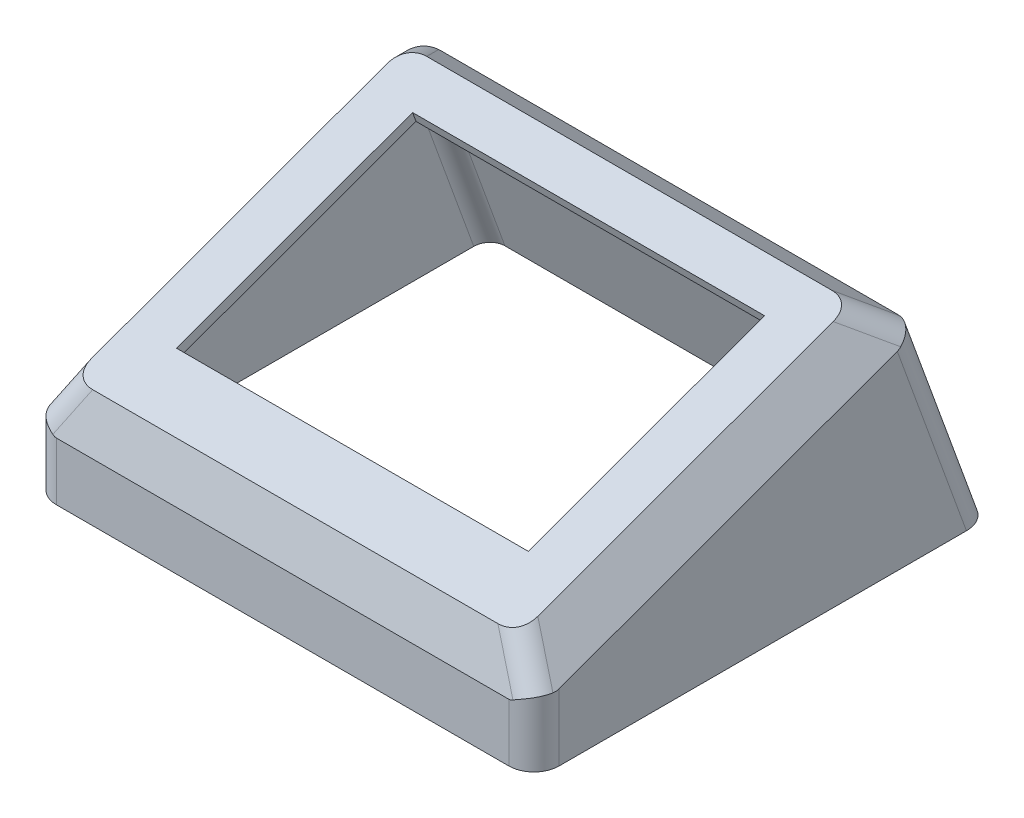
SolidWorks part; units mm, degrees
ref_plane "Front Plane" through (0, 0, 0) normal (0, 0, 1) x (1, 0, 0)
ref_plane "Top Plane" through (0, 0, 0) normal (0, 1, 0) x (1, 0, 0)
ref_plane "Right Plane" through (0, 0, 0) normal (1, 0, 0) x (0, 0, -1)
sketch "Sketch2" plane through (0, 0, 0) normal (1, 0, 0) x (0, 0, -1)
  line L0 (-74.2357, 0) -> (-74.2357, 20)
  line L1 (55, 0) -> (-55, 0) construction
  line L2 (-74.2357, 20) -> (0, 47.0196)
  line L3 (0, 55) -> (0, -55) construction
  line L4 (0, 47.0196) -> (17.1137, 0)
  line L5 (17.1137, 0) -> (-74.2357, 0)
  dimension "D1" = 79
  dimension "D2" = 20
  dimension "D3" = 110
extrude "Boss-Extrude1" add sketch "Sketch2" along normal blind 50 and the other way blind 50
chamfer "Chamfer3" distance 8 angle 35 3 edges at (50, 33.5098, 37.1179) (0, 47.0196, 0) (-50, 33.5098, 37.1179) first distance on face at (50, 16.7549, 32.8394) first distance on face at (0, 23.5098, -8.5569) first distance on face at (-50, 16.7549, 32.8394)
chamfer "Chamfer4" distance 8.5 angle 15 1 edges at (0, 20, 74.2357) first distance on face at (0, 10.4955, 74.2357)
fillet "Fillet7" radius 5 8 edges at (-50, 19.751, -9.9249) (50, 19.751, -9.9249) (-50, 5.7433, 74.2357) (50, 5.7433, 74.2357) (-47.1992, 42.3029, 1.2638) (-47.1948, 16.2093, 72.9739) (47.1992, 42.3029, 1.2638) (47.1948, 16.2093, 72.9739)
shell "Shell1" thickness 2 removed face at (0, 0, 28.6246)
sketch "Sketch3" plane through (0, 41.5193, 15.1118) normal (0, 0.9397, 0.342) x (1, 0, 0)
  line L0 (0, -55) -> (0, 55) construction
  line L1 (35, -48.157) -> (-35, -48.157)
  line L2 (35, -48.157) -> (35, 1.843)
  line L3 (35, 1.843) -> (-35, 1.843)
  line L4 (-35, -48.157) -> (-35, 1.843)
  line L5 (35, -48.157) -> (-35, 1.843) construction
  line L6 (35, 1.843) -> (-35, -48.157) construction
  point P0 (0, -23.157)
  dimension "D1" = 70
  dimension "D2" = 50
extrude "Cut-Extrude1" cut sketch "Sketch3" against normal up to surface (2 mm away) up to face at (0, 31.1317, 37.8039)
sketch "Sketch4" plane through (0, 5.5002, -15.1118) normal (0, 0.342, -0.9397) x (-1, 0, 0)
  line L1 (-8.6716, 19.762) -> (3.7813, 19.762)
  line L2 (-8.6716, 19.762) -> (-8.6716, 25.989)
  line L3 (-8.6716, 25.989) -> (3.7813, 25.989)
  line L4 (3.7813, 19.762) -> (3.7813, 25.989)
  line L7 (-20.912, 22.4396) -> (-11.9307, 22.4396)
  line L8 (-20.912, 22.4396) -> (-20.912, 25.6423)
  line L9 (-20.912, 25.6423) -> (-11.9307, 25.6423)
  line L10 (-11.9307, 22.4396) -> (-11.9307, 25.6423)
  line L11 (11.9318, 24.7569) -> (7.1813, 24.7569)
  line L12 (11.9318, 24.7569) -> (11.9318, 26.047)
  line L13 (11.9318, 26.047) -> (7.1813, 26.047)
  line L14 (7.1813, 24.7569) -> (7.1813, 26.047)
extrude "Cut-Extrude2" cut sketch "Sketch4" against normal up to surface (2 mm away) up to face at (0, 19.1127, -8.0289)
fillet "Fillet8" radius 1.25 4 edges at (20.912, 26.2445, -6.4973) (20.912, 29.2541, -5.4019) (11.9307, 29.2541, -5.4019) (11.9307, 26.2445, -6.4973)
